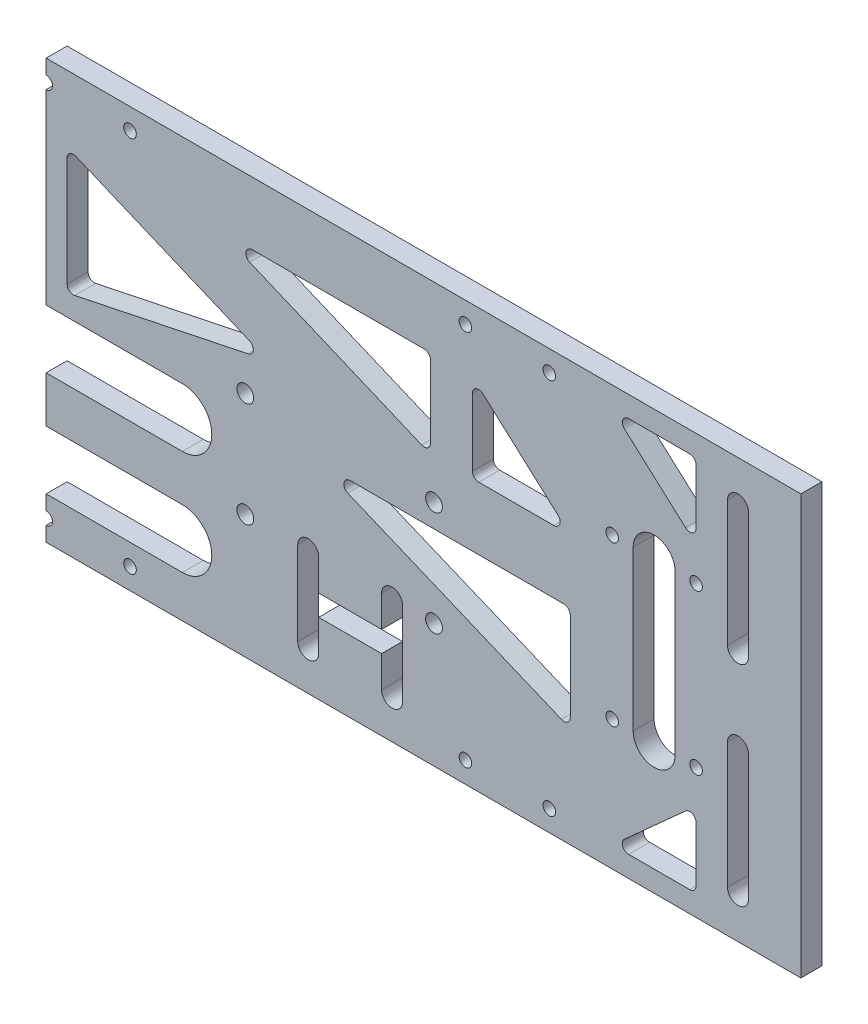
SolidWorks part; units mm, degrees
material "6061 合金"
ref_plane "前视基准面" through (0, 0, 0) normal (0, 0, 1) x (1, 0, 0)
ref_plane "上视基准面" through (0, 0, 0) normal (0, 1, 0) x (1, 0, 0)
ref_plane "右视基准面" through (0, 0, 0) normal (1, 0, 0) x (0, 0, -1)
sketch "草图1" plane through (0, 0, 0) normal (0, 0, 1) x (1, 0, 0)
  line L1 (0, 0) -> (320, 0)
  line L2 (0, 0) -> (0, 121)
  line L3 (0, 121) -> (320, 121)
  line L4 (320, 0) -> (320, 121)
  dimension "D1" = 320
  dimension "D2" = 121
extrude "凸台-拉伸1" add sketch "草图1" along normal blind 5
sketch "草图2" plane through (0, 0, 5) normal (0, 0, 1) x (1, 0, 0)
  line L0 (160, 121) -> (160, 0) construction
  line L1 (320, 121) -> (0, 121) construction
  line L2 (0, 0) -> (320, 0) construction
  line L3 (0, 121) -> (0, 0) construction
  line L4 (30, 0) -> (35, 0)
  line L5 (30, 0) -> (30, 30)
  line L6 (30, 30) -> (35, 30)
  line L7 (35, 0) -> (35, 30)
  line L8 (285, 0) -> (285, 30)
  line L9 (290, 30) -> (285, 30)
  line L10 (290, 0) -> (290, 30)
  line L11 (290, 0) -> (285, 0)
  dimension "D1" = 30
  dimension "D2" = 30
  dimension "D3" = 5
extrude "切除-拉伸1" cut sketch "草图2" against normal through all
sketch "草图3" plane through (0, 0, 5) normal (0, 0, 1) x (1, 0, 0)
  line L0 (40, 116) -> (60, 116) construction
  line L1 (160, 121) -> (160, 0) construction
  line L2 (320, 121) -> (0, 121) construction
  line L3 (35, 0) -> (285, 0) construction
  line L4 (140, 116) -> (160, 116) construction
  line L5 (0, 121) -> (0, 0) construction
  line L6 (280, 116) -> (260, 116) construction
  circle A0 centre (40, 116) radius 1.5
  circle A1 centre (60, 116) radius 1.5
  circle A2 centre (140, 116) radius 1.5
  circle A3 centre (160, 116) radius 1.5
  circle A4 centre (260, 116) radius 1.5
  circle A5 centre (280, 116) radius 1.5
  circle A6 centre (180, 116) radius 1.5
  dimension "D5" = 3
  dimension "D1" = 40
  dimension "D2" = 5
  dimension "D3" = 20
  dimension "D4" = 20
extrude "切除-拉伸2" cut sketch "草图3" against normal through all
sketch "草图4" plane through (0, 0, 5) normal (0, 0, 1) x (1, 0, 0)
  line L0 (160, 121) -> (160, 0) construction
  line L1 (5, 90) -> (25, 90) construction
  line L2 (5, 90) -> (5, 10) construction
  line L3 (5, 10) -> (25, 10) construction
  line L4 (25, 90) -> (25, 10) construction
  line L5 (320, 121) -> (0, 121) construction
  line L6 (35, 0) -> (285, 0) construction
  line L7 (0, 0) -> (30, 0) construction
  line L8 (0, 121) -> (0, 0) construction
  line L10 (295, 90) -> (295, 10) construction
  line L11 (315, 10) -> (295, 10) construction
  line L12 (315, 90) -> (315, 10) construction
  line L13 (315, 90) -> (295, 90) construction
  circle A0 centre (5, 90) radius 1.5
  circle A1 centre (25, 90) radius 1.5
  circle A2 centre (5, 10) radius 1.5
  circle A3 centre (25, 10) radius 1.5
  circle A4 centre (295, 10) radius 1.5
  circle A5 centre (315, 10) radius 1.5
  circle A6 centre (295, 90) radius 1.5
  circle A7 centre (315, 90) radius 1.5
  dimension "D5" = 3
  dimension "D1" = 10
  dimension "D2" = 80
  dimension "D3" = 5
  dimension "D4" = 20
extrude "切除-拉伸3" cut sketch "草图4" against normal through all
sketch "草图6" plane through (0, 0, 5) normal (0, 0, 1) x (1, 0, 0)
  line L0 (160, 121) -> (160, 0) construction
  line L1 (320, 121) -> (0, 121) construction
  line L2 (35, 0) -> (285, 0) construction
  line L3 (127.5, 63) -> (192.5, 63) construction
  line L4 (112.5, 50.5) -> (207.5, 50.5) construction
  line L5 (112.5, 50.5) -> (112.5, 75.5) construction
  line L6 (112.5, 75.5) -> (207.5, 75.5) construction
  line L7 (207.5, 50.5) -> (207.5, 75.5) construction
  line L8 (112.5, 50.5) -> (207.5, 75.5) construction
  line L9 (112.5, 75.5) -> (207.5, 50.5) construction
  line L10 (127.5, 70) -> (192.5, 70)
  line L11 (127.5, 56) -> (192.5, 56)
  circle A0 centre (112.5, 75.5) radius 2
  circle A1 centre (207.5, 75.5) radius 2
  circle A2 centre (207.5, 50.5) radius 2
  circle A3 centre (112.5, 50.5) radius 2
  arc A4 (127.5, 70) -> (127.5, 56) centre (127.5, 63) ccw
  arc A5 (192.5, 56) -> (192.5, 70) centre (192.5, 63) ccw
  point P6 (160, 63)
  point P17 (160, 63)
  dimension "D1" = 4
  dimension "D5" = 7
  dimension "D2" = 25
  dimension "D3" = 95
  dimension "D4" = 45.5
  dimension "D6" = 15
extrude "切除-拉伸5" cut sketch "草图6" against normal through all
sketch "草图5" plane through (0, 0, 5) normal (0, 0, 1) x (1, 0, 0)
  line L0 (5, 101.368) -> (5, 114.5)
  line L1 (6.5, 116) -> (21.0911, 116)
  line L2 (22.0945, 113.3851) -> (7.5034, 100.2531)
  line L6 (5, 90) -> (25, 90) construction
  line L7 (0, 121) -> (0, 0) construction
  line L8 (320, 121) -> (0, 121) construction
  line L9 (38.9089, 85) -> (56.8333, 85)
  line L10 (58.3333, 86.5) -> (58.3333, 102.632)
  line L11 (55.8299, 103.7469) -> (37.9055, 87.6149)
  line L12 (160, 121) -> (160, 0) construction
  line L13 (35, 0) -> (285, 0) construction
  line L14 (35, 68.5) -> (35, 47.25)
  line L15 (35, 0) -> (285, 0)
  line L16 (35, 0) -> (35, 30)
  line L17 (35, 30) -> (285, 30)
  line L18 (285, 0) -> (285, 30)
  line L19 (37.0769, 45.8654) -> (88.0769, 67.1154)
  line L20 (87.5, 70) -> (36.5, 70)
  line L24 (68.3333, 87.2569) -> (68.3333, 104.5)
  line L25 (69.8333, 106) -> (110.8883, 106)
  line L26 (111.4691, 103.117) -> (70.4142, 85.874)
  line L27 (111.7889, 84.0154) -> (153.1936, 75.3769)
  line L28 (155, 76.8453) -> (155, 102.8738)
  line L29 (152.9192, 104.2567) -> (111.5144, 86.8668)
  line L30 (315, 90) -> (295, 90) construction
  line L31 (167.0808, 104.2567) -> (208.4856, 86.8668)
  line L32 (165, 76.8453) -> (165, 102.8738)
  line L33 (208.2111, 84.0154) -> (166.8064, 75.3769)
  line L34 (208.5309, 103.117) -> (249.5858, 85.874)
  line L35 (250.1667, 106) -> (209.1117, 106)
  line L36 (251.6667, 87.2569) -> (251.6667, 104.5)
  line L40 (232.5, 70) -> (283.5, 70)
  line L41 (282.9231, 45.8654) -> (231.9231, 67.1154)
  line L42 (285, 68.5) -> (285, 47.25)
  line L43 (264.1701, 103.7469) -> (282.0945, 87.6149)
  line L44 (261.6667, 86.5) -> (261.6667, 102.632)
  line L45 (281.0911, 85) -> (263.1667, 85)
  line L46 (297.9055, 113.3851) -> (312.4966, 100.2531)
  line L47 (313.5, 116) -> (298.9089, 116)
  line L48 (315, 101.368) -> (315, 114.5)
  line L52 (192.5, 70) -> (127.5, 70) construction
  arc A2 (155, 102.8738) -> (152.9192, 104.2567) centre (153.5, 102.8738) ccw
  arc A4 (21.0911, 116) -> (22.0945, 113.3851) centre (21.0911, 114.5) cw
  arc A5 (5, 101.368) -> (7.5034, 100.2531) centre (6.5, 101.368) ccw
  arc A6 (5, 114.5) -> (6.5, 116) centre (6.5, 114.5) cw
  arc A7 (56.8333, 85) -> (58.3333, 86.5) centre (56.8333, 86.5) ccw
  arc A8 (38.9089, 85) -> (37.9055, 87.6149) centre (38.9089, 86.5) cw
  arc A9 (58.3333, 102.632) -> (55.8299, 103.7469) centre (56.8333, 102.632) ccw
  arc A10 (88.0769, 67.1154) -> (87.5, 70) centre (87.5, 68.5) ccw
  arc A11 (35, 47.25) -> (37.0769, 45.8654) centre (36.5, 47.25) ccw
  arc A12 (35, 68.5) -> (36.5, 70) centre (36.5, 68.5) cw
  arc A17 (153.1936, 75.3769) -> (155, 76.8453) centre (153.5, 76.8453) ccw
  arc A18 (111.7889, 84.0154) -> (111.5144, 86.8668) centre (112.0953, 85.4838) cw
  arc A19 (68.3333, 87.2569) -> (70.4142, 85.874) centre (69.8333, 87.2569) ccw
  arc A20 (68.3333, 104.5) -> (69.8333, 106) centre (69.8333, 104.5) cw
  arc A21 (110.8883, 106) -> (111.4691, 103.117) centre (110.8883, 104.5) cw
  arc A22 (209.1117, 106) -> (208.5309, 103.117) centre (209.1117, 104.5) ccw
  arc A23 (251.6667, 104.5) -> (250.1667, 106) centre (250.1667, 104.5) ccw
  arc A24 (251.6667, 87.2569) -> (249.5858, 85.874) centre (250.1667, 87.2569) cw
  arc A25 (208.2111, 84.0154) -> (208.4856, 86.8668) centre (207.9047, 85.4838) ccw
  arc A26 (166.8064, 75.3769) -> (165, 76.8453) centre (166.5, 76.8453) cw
  arc A30 (285, 68.5) -> (283.5, 70) centre (283.5, 68.5) ccw
  arc A31 (285, 47.25) -> (282.9231, 45.8654) centre (283.5, 47.25) cw
  arc A32 (231.9231, 67.1154) -> (232.5, 70) centre (232.5, 68.5) cw
  arc A33 (261.6667, 102.632) -> (264.1701, 103.7469) centre (263.1667, 102.632) cw
  arc A34 (281.0911, 85) -> (282.0945, 87.6149) centre (281.0911, 86.5) ccw
  arc A35 (263.1667, 85) -> (261.6667, 86.5) centre (263.1667, 86.5) cw
  arc A36 (315, 114.5) -> (313.5, 116) centre (313.5, 114.5) ccw
  arc A37 (315, 101.368) -> (312.4966, 100.2531) centre (313.5, 101.368) cw
  arc A38 (298.9089, 116) -> (297.9055, 113.3851) centre (298.9089, 114.5) ccw
  arc A39 (165, 102.8738) -> (167.0808, 104.2567) centre (166.5, 102.8738) cw
  point P23 (25, 116)
  point P26 (5, 98)
  point P29 (5, 116)
  point P40 (35, 85)
  point P43 (58.3333, 106)
  point P56 (95, 70)
  point P59 (35, 45)
  point P62 (35, 70)
  point P84 (155, 105.1307)
  point P87 (155, 75)
  point P90 (107.0698, 85)
  point P93 (68.3333, 85)
  point P96 (68.3333, 106)
  point P99 (118.3333, 106)
  point P156 (201.6667, 106)
  point P157 (251.6667, 106)
  point P158 (251.6667, 85)
  point P159 (212.9302, 85)
  point P160 (165, 75)
  point P161 (165, 105.1307)
  point P162 (285, 70)
  point P163 (285, 45)
  point P164 (225, 70)
  point P165 (261.6667, 106)
  point P166 (285, 85)
  point P167 (315, 116)
  point P168 (315, 98)
  point P169 (295, 116)
  point P186 (20, 15)
  point P189 (8, 15)
  point P192 (20, 25)
  point P202 (300, 25)
  point P203 (312, 15)
  point P204 (300, 15)
  dimension "D8" = 1.5
  dimension "D12" = 1.5
  dimension "D16" = 1.5
  dimension "D27" = 1.5
  dimension "D4" = 5
  dimension "D5" = 5
  dimension "D6" = 20
  dimension "D7" = 18
  dimension "D9" = 5
  dimension "D10" = 10
  dimension "D11" = 10
  dimension "D13" = 15
  dimension "D14" = 15
  dimension "D15" = 60
  dimension "D21" = 15
  dimension "D22" = 10
  dimension "D23" = 50
  dimension "D24" = 15
  dimension "D25" = 10
  dimension "D26" = 5
  dimension "D29" = 8
  dimension "D31" = 10
extrude "切除-拉伸4" cut sketch "草图5" against normal through all
sketch "草图7" plane through (0, 0, 0) normal (0, 0, -1) x (-1, 0, 0)
  line L0 (-290, 0) -> (-290, 30)
  line L1 (-290, 30) -> (-30, 30)
  line L2 (-30, 30) -> (-30, 0)
  line L3 (-30, 0) -> (-290, 0)
extrude "凸台-拉伸2" add sketch "草图7" against normal blind 5
sketch "草图8" plane through (0, 0, 0) normal (0, 0, -1) x (-1, 0, 0)
  line L0 (-320, 0) -> (-320, 21)
  line L1 (-320, 0) -> (-320, 121) construction
  line L2 (-320, 21) -> (0, 21)
  line L3 (0, 121) -> (0, 0) construction
  line L4 (0, 21) -> (0, 0)
  line L5 (0, 0) -> (-320, 0)
extrude "切除-拉伸6" cut sketch "草图8" against normal blind 5
sketch "草图9" plane through (0, 0, 0) normal (0, 0, -1) x (-1, 0, 0)
  line L0 (-160, 21) -> (-335, 21)
  line L1 (0, 21) -> (-320, 21) construction
  line L2 (-335, 21) -> (-335, 121)
  line L3 (-335, 121) -> (15, 121)
  line L4 (15, 121) -> (15, 21)
  line L5 (15, 21) -> (-160, 21)
  line L6 (0, 21) -> (0, 121)
  line L7 (-320, 21) -> (-320, 121)
extrude "凸台-拉伸3" add sketch "草图9" against normal blind 5 contours L0 L7 L3 L2 | L6 L5 L4 L3 region at (327.5, 71, 0) region at (-7.5, 71, 0)
sketch "草图10" plane through (0, 0, 0) normal (0, 0, -1) x (-1, 0, 0)
  line L0 (-335, 71) -> (-325, 71)
  line L1 (-335, 21) -> (-335, 121) construction
  line L2 (-325, 71) -> (-325, 121)
  line L3 (-335, 121) -> (15, 121) construction
  line L4 (-325, 71) -> (-325, 21)
  line L5 (15, 21) -> (-335, 21) construction
  line L6 (15, 71) -> (5, 71)
  line L7 (15, 121) -> (15, 21) construction
  line L8 (5, 71) -> (5, 121)
  line L9 (5, 71) -> (5, 21)
  line L10 (-325, 71) -> (-325, 81)
  line L11 (-325, 81) -> (-325, 111)
  line L12 (-325, 71) -> (-325, 61)
  line L13 (-325, 61) -> (-325, 31)
  line L14 (-325, 81) -> (-325, 111) construction
  line L15 (-327.5, 81) -> (-327.5, 111)
  line L16 (-322.5, 81) -> (-322.5, 111)
  line L17 (-325, 61) -> (-325, 31) construction
  line L18 (-322.5, 61) -> (-322.5, 31)
  line L19 (-327.5, 61) -> (-327.5, 31)
  line L20 (-160, 21) -> (-160, 121)
  line L21 (5, 61) -> (5, 31) construction
  line L22 (2.5, 61) -> (2.5, 31)
  line L23 (7.5, 61) -> (7.5, 31)
  line L24 (5, 81) -> (5, 111) construction
  line L25 (7.5, 81) -> (7.5, 111)
  line L26 (2.5, 81) -> (2.5, 111)
  arc A0 (-327.5, 81) -> (-322.5, 81) centre (-325, 81) ccw
  arc A1 (-322.5, 111) -> (-327.5, 111) centre (-325, 111) ccw
  arc A2 (-322.5, 61) -> (-327.5, 61) centre (-325, 61) ccw
  arc A3 (-327.5, 31) -> (-322.5, 31) centre (-325, 31) ccw
  arc A4 (2.5, 61) -> (7.5, 61) centre (5, 61) cw
  arc A5 (7.5, 31) -> (2.5, 31) centre (5, 31) cw
  arc A6 (7.5, 81) -> (2.5, 81) centre (5, 81) cw
  arc A7 (2.5, 111) -> (7.5, 111) centre (5, 111) cw
  point P20 (-325, 96)
  point P25 (-325, 46)
  point P34 (5, 46)
  point P41 (5, 96)
  dimension "D1" = 10
  dimension "D2" = 10
  dimension "D3" = 30
  dimension "D4" = 10
  dimension "D5" = 30
extrude "切除-拉伸7" cut sketch "草图10" against normal blind 5 contours L16 A1 L2 L10 A0 | L2 A1 L15 A0 L10 | L4 A3 L18 A2 L12 | L19 A3 L4 L12 A2 | A7 L8 A6 L25 | A7 L26 A6 L8 | A5 L23 A4 L9 | A5 L9 A4 L22 region at (326.2281, 96, 0) region at (323.7719, 96, 0) region at (323.7719, 46, 0) region at (326.2281, 46, 0) region at (-3.7719, 96, 0) region at (-6.2281, 96, 0) region at (-6.2281, 46, 0) region at (-3.7719, 46, 0)
sketch "草图13" plane through (0, 0, 0) normal (0, 0, -1) x (-1, 0, 0)
  line L12 (-192.5, 63) -> (-192.5, 38)
  line L13 (-127.5, 63) -> (-127.5, 38)
  line L14 (-192.5, 38) -> (-127.5, 38) construction
  line L15 (-192.5, 45) -> (-127.5, 45)
  line L16 (-192.5, 31) -> (-127.5, 31)
  line L18 (-305, 63.5) -> (-305, 83.5)
  line L19 (-305, 63.5) -> (-305, 48.5)
  line L23 (-160, 21) -> (-160, 121)
  line L24 (15, 21) -> (-335, 21) construction
  line L25 (-335, 121) -> (15, 121) construction
  arc A1 (-192.5, 45) -> (-192.5, 31) centre (-192.5, 38) ccw
  arc A2 (-127.5, 31) -> (-127.5, 45) centre (-127.5, 38) ccw
  point P16 (-160, 38)
  dimension "D1" = 25
  dimension "D3" = 15
  dimension "D2" = 25
  dimension "D4" = 20
extrude "切除-拉伸8" cut sketch "草图13" against normal blind 5 contours L16 A2 L15 L23 | A1 L16 L23 L15 | L16 A2 L15 A1 region at (179.031, 38, 0) region at (140.969, 38, 0)
sketch "草图15" plane through (0, 0, 0) normal (0, 0, -1) x (-1, 0, 0)
  line L0 (-313.5, 116) -> (-298.9089, 116)
  line L1 (-297.9055, 113.3851) -> (-312.4966, 100.2531)
  line L2 (-315, 114.5) -> (-315, 101.368)
  line L3 (-21.0911, 116) -> (-6.5, 116)
  line L4 (-5, 114.5) -> (-5, 101.368)
  line L5 (-7.5034, 100.2531) -> (-22.0945, 113.3851)
  line L6 (-335, 71) -> (15, 71)
  line L7 (-335, 21) -> (-335, 121) construction
  line L8 (15, 121) -> (15, 21) construction
  line L9 (-21.0911, 26) -> (-6.5, 26)
  line L10 (-5, 27.5) -> (-5, 40.632)
  line L11 (-7.5034, 41.7469) -> (-22.0945, 28.6149)
  line L12 (-315, 27.5) -> (-315, 40.632)
  line L13 (-313.5, 26) -> (-298.9089, 26)
  line L14 (-297.9055, 28.6149) -> (-312.4966, 41.7469)
  circle A0 centre (-280, 116) radius 1.5
  circle A1 centre (-260, 116) radius 1.5
  circle A2 centre (-180, 116) radius 1.5
  circle A3 centre (-160, 116) radius 1.5
  circle A4 centre (-140, 116) radius 1.5
  circle A5 centre (-60, 116) radius 1.5
  circle A6 centre (-40, 116) radius 1.5
  circle A7 centre (-25, 90) radius 1.5
  circle A8 centre (-5, 90) radius 1.5
  circle A9 centre (-315, 90) radius 1.5
  circle A10 centre (-295, 90) radius 1.5
  arc A11 (-315, 101.368) -> (-312.4966, 100.2531) centre (-313.5, 101.368) ccw
  arc A12 (-313.5, 116) -> (-315, 114.5) centre (-313.5, 114.5) ccw
  arc A13 (-297.9055, 113.3851) -> (-298.9089, 116) centre (-298.9089, 114.5) ccw
  arc A14 (-21.0911, 116) -> (-22.0945, 113.3851) centre (-21.0911, 114.5) ccw
  arc A15 (-5, 114.5) -> (-6.5, 116) centre (-6.5, 114.5) ccw
  arc A16 (-7.5034, 100.2531) -> (-5, 101.368) centre (-6.5, 101.368) ccw
  circle A17 centre (-25, 52) radius 1.5
  circle A18 centre (-5, 52) radius 1.5
  arc A19 (-5, 27.5) -> (-6.5, 26) centre (-6.5, 27.5) cw
  arc A20 (-7.5034, 41.7469) -> (-5, 40.632) centre (-6.5, 40.632) cw
  arc A21 (-21.0911, 26) -> (-22.0945, 28.6149) centre (-21.0911, 27.5) cw
  circle A22 centre (-40, 26) radius 1.5
  circle A23 centre (-60, 26) radius 1.5
  circle A24 centre (-140, 26) radius 1.5
  circle A25 centre (-160, 26) radius 1.5
  circle A26 centre (-180, 26) radius 1.5
  circle A27 centre (-260, 26) radius 1.5
  circle A28 centre (-280, 26) radius 1.5
  arc A29 (-313.5, 26) -> (-315, 27.5) centre (-313.5, 27.5) cw
  arc A30 (-297.9055, 28.6149) -> (-298.9089, 26) centre (-298.9089, 27.5) cw
  arc A31 (-315, 40.632) -> (-312.4966, 41.7469) centre (-313.5, 40.632) cw
  circle A32 centre (-295, 52) radius 1.5
  circle A33 centre (-315, 52) radius 1.5
extrude "切除-拉伸9" cut sketch "草图15" against normal through all contours A33 | A31 L12 A29 L13 A30 L14 | A32 | A28 | A27 | A26 | A25 | A24 | A23 | A22 | A21 L9 A19 L10 A20 L11 | A18 | A17 region at (11.5603, 31.9627, 0) region at (308.4397, 31.9627, 0) region at (25, 52, 0) region at (5, 52, 0) region at (40, 26, 0) region at (60, 26, 0) region at (140, 26, 0) region at (160, 26, 0) region at (180, 26, 0) region at (260, 26, 0) region at (280, 26, 0) region at (295, 52, 0) region at (315, 52, 0)
sketch "草图16" plane through (0, 0, 0) normal (0, 0, -1) x (-1, 0, 0)
  line L0 (-335, 71) -> (15, 71)
  line L1 (-335, 21) -> (-335, 121) construction
  line L2 (15, 121) -> (15, 21) construction
  line L3 (-315, 90) -> (-295, 90)
  line L4 (-315, 52) -> (-295, 52)
  line L5 (-305, 52) -> (-305, 90)
  line L6 (-305, 52) -> (-305, 90) construction
  line L7 (-310, 52) -> (-310, 90)
  line L8 (-300, 52) -> (-300, 90)
  line L9 (-160, 21) -> (-160, 121)
  line L10 (15, 21) -> (-335, 21) construction
  line L11 (-335, 121) -> (15, 121) construction
  line L12 (-15, 52) -> (-15, 90) construction
  line L13 (-10, 52) -> (-10, 90)
  line L14 (-20, 52) -> (-20, 90)
  arc A0 (-310, 52) -> (-300, 52) centre (-305, 52) ccw
  arc A1 (-300, 90) -> (-310, 90) centre (-305, 90) ccw
  arc A2 (-10, 52) -> (-20, 52) centre (-15, 52) cw
  arc A3 (-20, 90) -> (-10, 90) centre (-15, 90) cw
  point P16 (-305, 71)
  point P29 (-15, 71)
extrude "切除-拉伸10" cut sketch "草图16" against normal through all contours L4 L8 L0 L5 | L4 A0 | L7 L4 L5 L0 | L0 L8 L3 L5 | L7 L0 L5 L3 | L3 A1 | A2 L13 L0 L14 | A3 L14 L0 L13 region at (307.5, 80.5, 0) region at (307.5, 61.5, 0) region at (15, 82.4907, 0) region at (15, 59.5093, 0) region at (302.5, 80.5, 0) region at (302.5, 61.5, 0) region at (305, 49.8779, 0) region at (305, 92.1221, 0)
sketch "草图17" plane through (0, 0, 0) normal (0, 0, -1) x (-1, 0, 0)
  line L0 (-207.5, 50.5) -> (-257.5, 50.5)
  line L1 (-257.5, 50.5) -> (-257.5, 30.5)
  line L2 (-257.5, 30.5) -> (-207.5, 30.5)
  line L3 (-207.5, 30.5) -> (-207.5, 50.5)
  line L4 (-207.5, 40.5) -> (-257.5, 40.5)
  line L5 (-257.5, 50.5) -> (-247.5, 50.5)
  line L6 (-247.5, 50.5) -> (-247.5, 30.5)
  line L7 (-207.5, 50.5) -> (-217.5, 50.5)
  line L8 (-217.5, 50.5) -> (-217.5, 30.5)
  line L9 (-247.5, 50.5) -> (-242.5, 50.5)
  line L10 (-242.5, 50.5) -> (-242.5, 30.5)
  line L11 (-217.5, 50.5) -> (-222.5, 50.5)
  line L12 (-222.5, 50.5) -> (-222.5, 30.5)
  line L13 (-242.5, 50.5) -> (-242.5, 30.5) construction
  line L14 (-240, 50.5) -> (-240, 30.5)
  line L15 (-245, 50.5) -> (-245, 30.5)
  line L16 (-222.5, 50.5) -> (-222.5, 30.5) construction
  line L17 (-220, 50.5) -> (-220, 30.5)
  line L18 (-225, 50.5) -> (-225, 30.5)
  line L19 (-242.5, 40.5) -> (-222.5, 40.5) construction
  line L20 (-242.5, 43) -> (-222.5, 43)
  line L21 (-242.5, 38) -> (-222.5, 38)
  line L22 (-160, 21) -> (-160, 121)
  line L23 (15, 21) -> (-335, 21) construction
  line L24 (-335, 121) -> (15, 121) construction
  line L25 (-97.5, 50.5) -> (-97.5, 30.5) construction
  line L26 (-100, 50.5) -> (-100, 30.5)
  line L27 (-95, 50.5) -> (-95, 30.5)
  line L28 (-77.5, 40.5) -> (-97.5, 40.5) construction
  line L29 (-77.5, 43) -> (-97.5, 43)
  line L30 (-77.5, 38) -> (-97.5, 38)
  line L31 (-77.5, 50.5) -> (-77.5, 30.5) construction
  line L32 (-80, 50.5) -> (-80, 30.5)
  line L33 (-75, 50.5) -> (-75, 30.5)
  arc A0 (-240, 50.5) -> (-245, 50.5) centre (-242.5, 50.5) ccw
  arc A1 (-245, 30.5) -> (-240, 30.5) centre (-242.5, 30.5) ccw
  arc A2 (-220, 50.5) -> (-225, 50.5) centre (-222.5, 50.5) ccw
  arc A3 (-225, 30.5) -> (-220, 30.5) centre (-222.5, 30.5) ccw
  arc A4 (-242.5, 43) -> (-242.5, 38) centre (-242.5, 40.5) ccw
  arc A5 (-222.5, 38) -> (-222.5, 43) centre (-222.5, 40.5) ccw
  arc A6 (-100, 50.5) -> (-95, 50.5) centre (-97.5, 50.5) cw
  arc A7 (-95, 30.5) -> (-100, 30.5) centre (-97.5, 30.5) cw
  arc A8 (-77.5, 43) -> (-77.5, 38) centre (-77.5, 40.5) cw
  arc A9 (-97.5, 38) -> (-97.5, 43) centre (-97.5, 40.5) cw
  arc A10 (-80, 50.5) -> (-75, 50.5) centre (-77.5, 50.5) cw
  arc A11 (-75, 30.5) -> (-80, 30.5) centre (-77.5, 30.5) cw
  point P11 (-242.5, 40.5)
  point P20 (-222.5, 40.5)
  point P25 (-232.5, 40.5)
  point P40 (-97.5, 40.5)
  point P47 (-87.5, 40.5)
  point P54 (-77.5, 40.5)
  dimension "D1" = 20
extrude "切除-拉伸11" cut sketch "草图17" against normal through all contours A11 L33 A8 L30 L32 | A8 L29 L32 L30 | A10 L32 L29 A8 L33 | L32 L29 L27 L30 | A9 L30 L27 L29 | L26 A9 L29 L27 A6 | L30 A9 L26 A7 L27 | L10 L20 L14 L0 | A4 L10 L0 L15 | L0 A0 | L20 L14 L4 L18 | L20 L10 L4 L14 | L10 A4 L4 | L4 A4 L10 | L10 L21 L14 L4 | L14 L21 L18 L4 | L21 L10 L2 L14 | A4 L15 L2 L10 | L2 A1 | L2 A3 | A5 L12 L2 L17 | L21 L18 L2 L12 | L18 L21 L12 L4 | L12 A5 L4 | L4 A5 L12 | L20 L18 L4 L12 | L18 L20 L12 L0 | A5 L17 L11 L12 | L11 A2 L0 region at (221.2038, 46.4624, 0) region at (222.5, 51.561, 0) region at (223.75, 46.75, 0) region at (221.439, 39.439, 0) region at (221.2038, 34.5376, 0) region at (221.439, 41.561, 0) region at (223.75, 41.75, 0) region at (223.75, 39.25, 0) region at (222.5, 29.439, 0) region at (223.75, 34.25, 0) region at (241.25, 46.75, 0) region at (242.5, 51.561, 0) region at (232.5, 41.75, 0) region at (232.5, 39.25, 0) region at (243.7962, 46.4624, 0) region at (241.25, 41.75, 0) region at (241.25, 39.25, 0) region at (242.5, 29.439, 0) region at (241.25, 34.25, 0) region at (243.561, 41.561, 0) region at (243.7962, 34.5376, 0) region at (243.561, 39.439, 0) region at (97.5535, 47.6019, 0) region at (97.5535, 33.3981, 0) region at (97.2666, 40.5, 0) region at (87.5, 40.5, 0) region at (77.4465, 47.6019, 0) region at (77.7334, 40.5, 0) region at (77.4465, 33.3981, 0)
sketch "草图18" plane through (0, 0, 0) normal (0, 0, -1) x (-1, 0, 0)
  line L0 (-335, 21) -> (-340, 21)
  line L1 (-340, 21) -> (-340, 121)
  line L2 (-340, 121) -> (-335, 121)
  line L3 (-335, 121) -> (-335, 21)
  line L4 (15, 21) -> (20, 21)
  line L5 (20, 21) -> (20, 121)
  line L6 (20, 121) -> (15, 121)
  line L7 (15, 121) -> (15, 21)
extrude "凸台-拉伸4" add sketch "草图18" against normal blind 5
sketch "草图19" plane through (0, 0, 5) normal (0, 0, 1) x (1, 0, 0)
  line L0 (160, 121) -> (160, 21)
  line L1 (340, 121) -> (-20, 121) construction
  line L2 (-20, 21) -> (340, 21) construction
  line L3 (160, 21) -> (340, 21)
  line L4 (340, 21) -> (340, 121)
  line L5 (340, 121) -> (160, 121)
  line L6 (160, 121) -> (-20, 121)
  line L7 (-20, 121) -> (-20, 21)
  line L8 (-20, 21) -> (160, 21)
extrude "切除-拉伸12" cut sketch "草图19" against normal blind 10 contours L7 L8 L0 L6 region at (70, 71, 5)
sketch "草图20" plane through (0, 0, 5) normal (0, 0, 1) x (1, 0, 0)
  line L0 (207.5, 75.5) -> (252.5, 75.5)
  line L1 (207.5, 50.5) -> (252.5, 50.5)
  circle A0 centre (252.5, 75.5) radius 2
  circle A1 centre (252.5, 50.5) radius 2
extrude "切除-拉伸13" cut sketch "草图20" against normal blind 10 contours A0 | A1 region at (252.5, 73.5566, 5) region at (252.5, 48.5566, 5)
